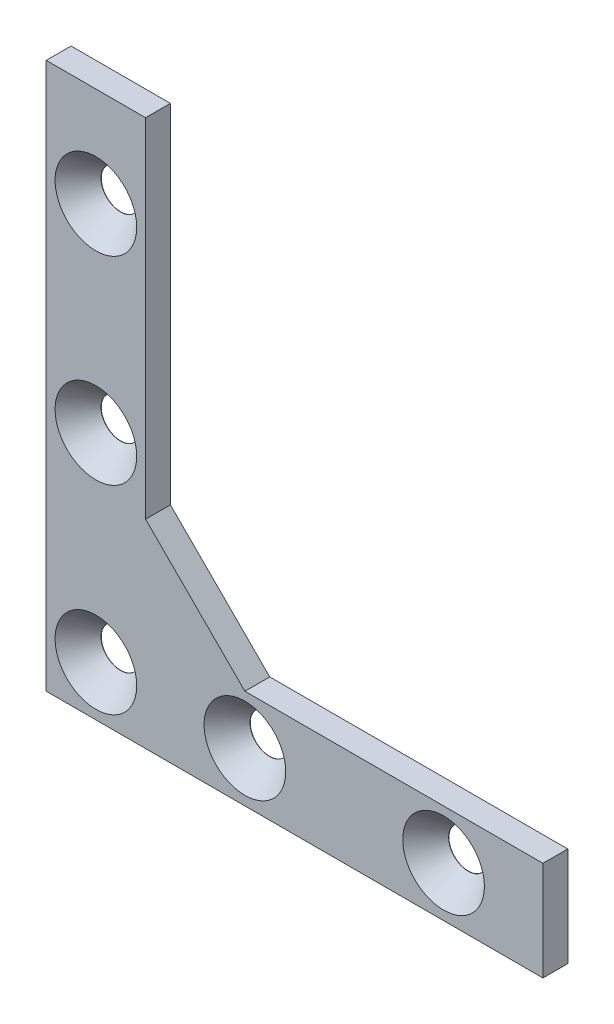
SolidWorks part; units mm, degrees
material "6061 Alloy"
ref_plane "Front Plane" through (0, 0, 0) normal (0, 0, 1) x (1, 0, 0)
ref_plane "Top Plane" through (0, 0, 0) normal (0, 1, 0) x (1, 0, 0)
ref_plane "Right Plane" through (0, 0, 0) normal (1, 0, 0) x (0, 0, -1)
sketch "Sketch1" plane through (0, 0, 0) normal (0, 0, 1) x (1, 0, 0)
  line L1 (-273.4534, -6.35) -> (-273.4534, 63.5)
  line L2 (-273.4534, 63.5) -> (-260.7534, 63.5)
  line L3 (-273.4534, -6.35) -> (-209.9534, -6.35)
  line L10 (-260.7534, 19.05) -> (-260.7534, 63.5)
  line L11 (-209.9534, -6.35) -> (-209.9534, 6.35)
  line L12 (-209.9534, 6.35) -> (-248.0534, 6.35)
  line L13 (-248.0534, 6.35) -> (-260.7534, 19.05)
  dimension "D1" = 69.85
  dimension "D2" = 63.5
  dimension "D3" = 12.7
  dimension "D4" = 38.1
  dimension "D5" = 12.7
  dimension "D6" = 44.45
extrude "Boss-Extrude1" add sketch "Sketch1" along normal blind 3.175
sketch "Sketch2" plane through (0, 0, 3.175) normal (0, 0, 1) x (1, 0, 0)
  line L0 (-267.1034, 63.5) -> (-267.1034, 50.8) construction
  line L1 (-260.7534, 63.5) -> (-273.4534, 63.5) construction
  line L2 (-267.1034, 50.8) -> (-267.1034, 25.4382) construction
  line L3 (-267.1034, 0.0382) -> (-248.0534, 0.0382) construction
  line L4 (-267.1034, 25.4382) -> (-267.1034, 0.0382) construction
  line L5 (-248.0534, 0.0382) -> (-222.6534, 0.0382) construction
  line L6 (-209.7517, 0) -> (-222.6534, 0.0382) construction
  dimension "D1" = 25.4
  dimension "D2" = 19.05
  dimension "D3" = 25.4
hole_wizard "#10 Clearance Hole1" positions "Sketch3" profile "Sketch4" hole size "#10" standard "ANSI Inch" end condition through all
sketch "Sketch3" plane through (0, 0, 3.175) normal (0, 0, 1) x (1, 0, 0)
  point P0 (-267.1034, 0.0382)
  point P3 (-267.1034, 25.4382)
  point P6 (-267.1034, 50.8)
  point P9 (-248.0534, 0.0382)
  point P12 (-222.6534, 0.0382)
sketch "Sketch4" plane through (-267.1034, 0.0382, 3.175) normal (1, 0, 0) x (0, -1, 0)
  line L0 (0, 0) -> (0, 3.175)
  line L1 (0, 3.175) -> (2.4892, 3.175)
  line L2 (2.4892, 3.175) -> (2.4892, 3.1411)
  line L3 (2.4892, 3.1411) -> (5.2197, 0)
  line L5 (5.2197, 0) -> (0, 0)
  line L6 (-2.4892, 3.1411) -> (-5.2197, 0) construction
  line L11 (0, -6.35) -> (0, 107.95) construction
  dimension "Thru Hole Dia." = 4.9784
  dimension "Thru Hole Depth" = 3.175
  dimension "Near C'Sink Dia." = 10.4394
  dimension "Near C'Sink Angle" = 82
